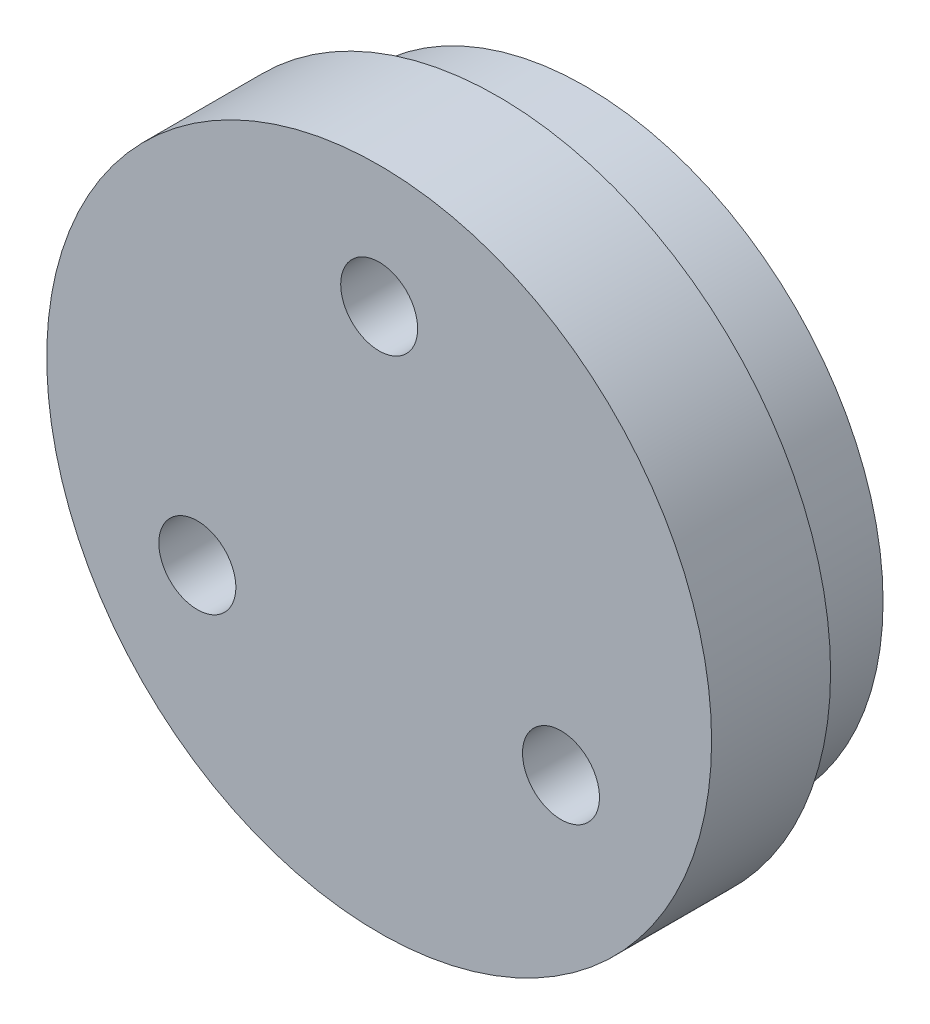
SolidWorks part; units mm, degrees
material "ABS"
ref_plane "正面" through (0, 0, 0) normal (0, 0, 1) x (1, 0, 0)
ref_plane "平面" through (0, 0, 0) normal (0, 1, 0) x (1, 0, 0)
ref_plane "右側面" through (0, 0, 0) normal (1, 0, 0) x (0, 0, -1)
sketch "ｽｹｯﾁ1" plane through (0, 0, 0) normal (0, 0, 1) x (1, 0, 0)
  circle A0 centre (0, 0) radius 8.5
  dimension "D1" = 17
extrude "ﾎﾞｽ - 押し出し1" add sketch "ｽｹｯﾁ1" along normal blind 2.5
sketch "ｽｹｯﾁ2" plane through (0, 0, 2.5) normal (0, 0, 1) x (1, 0, 0)
  circle A0 centre (0, 0) radius 9.5
  dimension "D1" = 19
extrude "ﾎﾞｽ - 押し出し2" add sketch "ｽｹｯﾁ2" along normal blind 3.4
sketch "ｽｹｯﾁ3" plane through (0, 0, 0) normal (0, 0, -1) x (-1, 0, 0)
  circle A0 centre (0, 0) radius 6 construction
  circle A1 centre (0, 6) radius 1.1
  circle A2 centre (5.1962, -3) radius 1.1
  circle A3 centre (-5.1962, -3) radius 1.1
  point P11 (0, 0)
  dimension "D1" = 12
  dimension "D2" = 2.2
  dimension "D3" = 3
extrude "ｶｯﾄ - 押し出し1" cut sketch "ｽｹｯﾁ3" against normal through all
